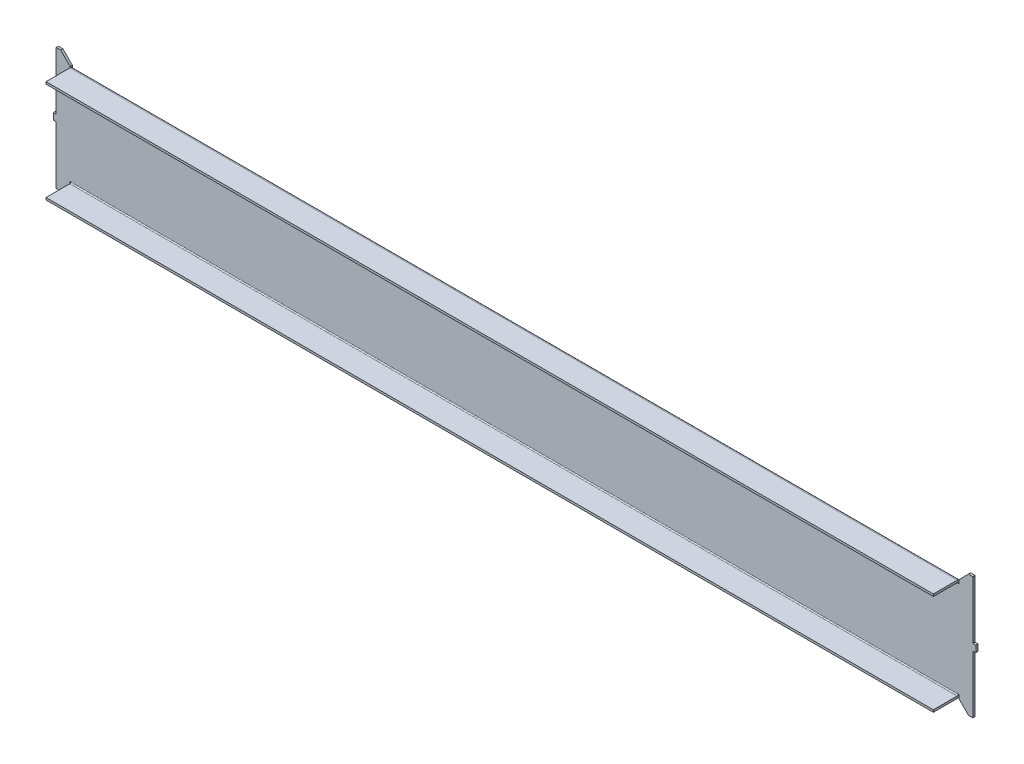
SolidWorks part; units mm, degrees
note: The reader was unsure of these and kept them because the rebuilt part matched: flange length of "Ребро-кромка1".
ref_plane "Спереди" through (0, 0, 0) normal (0, 0, 1) x (1, 0, 0)
ref_plane "Сверху" through (0, 0, 0) normal (0, 1, 0) x (1, 0, 0)
ref_plane "Справа" through (0, 0, 0) normal (1, 0, 0) x (0, 0, -1)
sketch "Эскиз1" plane through (0, 0, 0) normal (0, 0, 1) x (1, 0, 0)
  line L1 (-313, -35) -> (313, -35)
  line L2 (-313, -35) -> (-313, 35)
  line L3 (-313, 35) -> (313, 35)
  line L4 (313, -35) -> (313, 35)
  line L5 (-313, -35) -> (313, 35) construction
  line L6 (-313, 35) -> (313, -35) construction
  point P0 (0, 0)
  dimension "D1" = 70
  dimension "D2" = 626
base flange "Базовая кромка1" sketch "Эскиз1" thickness 1.5 reverse thickness direction no parameters "D1"=0.7366
edge flange "Ребро-кромка1" sketch "Эскиз5" flange profiles "Эскиз5", "Эскиз7" flange angle 90 flange length 18.5 flange position material inside bend radius 0.7366 thickness 1.5 relief rectangular parameters "D6"=10, "D8"=1
sketch "Эскиз5" plane through (0, 35, 0) normal (0, 1, 0) x (-1, 0, 0)
  line L0 (-313, 0) -> (313, 0) construction
  line L1 (-313, 0) -> (313, 0)
  line L2 (-313, 0) -> (-313, 17)
  line L3 (-313, 17) -> (313, 17)
  line L4 (313, 17) -> (313, 0)
sketch "Эскиз7" plane through (0, -35, 0) normal (0, -1, 0) x (1, 0, 0)
  line L0 (-313, 0) -> (313, 0) construction
  line L1 (-313, 0) -> (313, 0)
  line L2 (-313, 0) -> (-313, 17)
  line L3 (-313, 17) -> (313, 17)
  line L4 (313, 17) -> (313, 0)
bend "EdgeBend1" bend radius 0.7366 bend angle 90 parameters "D5"=1
bend "EdgeBend2" bend radius 0.7366 bend angle 90 parameters "D5"=3
sketch "Эскиз8" plane through (0, 0, 0) normal (0, 0, 1) x (1, 0, 0)
  line L0 (-313, 32.7634) -> (-313, -32.7634) construction
  line L1 (-315, 2.25) -> (-313, 2.25)
  line L2 (-315, 2.25) -> (-315, -2.25)
  line L3 (-315, -2.25) -> (-313, -2.25)
  line L4 (-313, 2.25) -> (-313, -2.25)
  line L5 (-315, 2.25) -> (-313, -2.25) construction
  line L6 (-315, -2.25) -> (-313, 2.25) construction
  line L7 (0, 0) -> (0, 80.527) construction
  line L8 (315, -2.25) -> (313, 2.25) construction
  line L9 (315, 2.25) -> (313, -2.25) construction
  line L10 (313, 2.25) -> (313, -2.25)
  line L11 (315, -2.25) -> (313, -2.25)
  line L12 (315, 2.25) -> (315, -2.25)
  line L13 (315, 2.25) -> (313, 2.25)
  point P0 (-314, 0)
  point P14 (314, 0)
  dimension "D1" = 2
  dimension "D2" = 4.5
base flange "Выступ1" sketch "Эскиз8" thickness 1.5 reverse thickness direction no parameters "D1"=0.7366
sketch "Эскиз11" plane through (0, 0, 17) normal (0, 0, 1) x (1, 0, 0)
  line L0 (-313, 32.7634) -> (313, 32.7634) construction
  line L1 (-313, 35) -> (-303, 35)
  line L2 (-313, 35) -> (-313, 32.7634)
  line L3 (-313, 32.7634) -> (-303, 32.7634)
  line L4 (-303, 35) -> (-303, 32.7634)
  line L5 (0, 0) -> (0, 79.6562) construction
  line L6 (0, 0) -> (58.6541, 0) construction
  line L7 (-303, -35) -> (-303, -32.7634)
  line L8 (-313, -32.7634) -> (-303, -32.7634)
  line L9 (-313, -35) -> (-313, -32.7634)
  line L10 (-313, -35) -> (-303, -35)
  line L11 (313, -35) -> (303, -35)
  line L12 (313, -35) -> (313, -32.7634)
  line L13 (313, -32.7634) -> (303, -32.7634)
  line L14 (303, -35) -> (303, -32.7634)
  line L15 (303, 35) -> (303, 32.7634)
  line L16 (313, 32.7634) -> (303, 32.7634)
  line L17 (313, 35) -> (313, 32.7634)
  line L18 (313, 35) -> (303, 35)
  dimension "D1" = 10
extrude "Вырез-Вытянуть1" cut sketch "Эскиз11" against normal up to surface (18.5 mm away) normal cut yes
sketch "Эскиз12" plane through (0, 0, 0) normal (0, 0, 1) x (1, 0, 0)
  line L0 (-313, 32.7634) -> (-313, 41.7634)
  line L1 (-313, 41.7634) -> (-310, 41.7634)
  line L2 (-310, 41.7634) -> (-303.5, 35.2634)
  line L3 (-303.5, 35.2634) -> (-303.5, 32.7634)
  line L4 (-313, 32.7634) -> (-303, 32.7634) construction
  line L5 (-303.5, 32.7634) -> (-313, 32.7634)
  line L6 (-303, 35) -> (-303, 33.5) construction
  line L7 (0, 0) -> (0, 105.8944) construction
  line L8 (0, 0) -> (116.0078, 0) construction
  line L9 (-303.5, -32.7634) -> (-313, -32.7634)
  line L10 (-303.5, -35.2634) -> (-303.5, -32.7634)
  line L11 (-310, -41.7634) -> (-303.5, -35.2634)
  line L12 (-313, -41.7634) -> (-310, -41.7634)
  line L13 (-313, -32.7634) -> (-313, -41.7634)
  line L14 (313, -32.7634) -> (313, -41.7634)
  line L15 (313, -41.7634) -> (310, -41.7634)
  line L16 (310, -41.7634) -> (303.5, -35.2634)
  line L17 (303.5, -35.2634) -> (303.5, -32.7634)
  line L18 (303.5, -32.7634) -> (313, -32.7634)
  line L19 (303.5, 32.7634) -> (313, 32.7634)
  line L20 (303.5, 35.2634) -> (303.5, 32.7634)
  line L21 (310, 41.7634) -> (303.5, 35.2634)
  line L22 (313, 41.7634) -> (310, 41.7634)
  line L23 (313, 32.7634) -> (313, 41.7634)
  dimension "D1" = 0.5
  dimension "D2" = 45
  dimension "D3" = 9
  dimension "D4" = 2.5
base flange "Выступ2" sketch "Эскиз12" thickness 1.5 reverse thickness direction no parameters "D1"=0.7366
sketch "Эскиз13" plane through (0, 0, 0) normal (0, 0, 1) x (1, 0, 0)
  line L0 (-270, 22) -> (-222, 22) construction
  line L1 (-303, 35) -> (-303, 33.5) construction
  line L2 (-303, 33.5) -> (303, 33.5) construction
  line L3 (0, 0) -> (0, 82.9755) construction
  line L4 (270, 22) -> (222, 22) construction
  circle A0 centre (-270, 22) radius 3.25
  circle A1 centre (-222, 22) radius 3.25
  circle A2 centre (222, 22) radius 3.25
  circle A3 centre (270, 22) radius 3.25
  dimension "D1" = 6.5
  dimension "D2" = 48
  dimension "D3" = 33
  dimension "D4" = 11.5
extrude "Вырез-Вытянуть2" cut sketch "Эскиз13" against normal blind 1.5 normal cut yes
sketch "Сгиб-Линии1" [suppressed] plane through (0, 0, 0) normal (0, 1, 0) x (1, 0, 0)
sketch "Граничная рамка1" [suppressed] plane through (0, 0, 0) normal (0, 1, 0) x (1, 0, 0)
sheet metal parameters "Листовой металл3" thickness 1.5 parameters "D1"=0.7366
flat pattern "Развертка3" [suppressed]
sketch "Сгиб-Линии2" plane through (0, 0, 0) normal (0, 1, 0) x (1, 0, 0)
sketch "Граничная рамка2" [suppressed] plane through (0, 0, 0) normal (0, 1, 0) x (1, 0, 0)
sheet metal parameters "Листовой металл7" thickness 1.5 parameters "D1"=0.7366
flat pattern "Развертка3" [suppressed]
sketch "Сгиб-Линии2" plane through (0, 0, 0) normal (0, 1, 0) x (1, 0, 0)
sketch "Граничная рамка2" [suppressed] plane through (0, 0, 0) normal (0, 1, 0) x (1, 0, 0)
bend of the flat pattern "Плоское состояние-<EdgeBend1>1"
bend of the flat pattern "Плоское состояние-<EdgeBend2>1"
sheet metal parameters "Листовой металл8" thickness 1.5 parameters "D1"=0.7366
flat pattern "Развертка8" [suppressed]
sketch "Сгиб-Линии3" plane through (0, 0, 0) normal (0, 1, 0) x (1, 0, 0)
sketch "Граничная рамка3" [suppressed] plane through (0, 0, 0) normal (0, 1, 0) x (1, 0, 0)
bend of the flat pattern "Плоское состояние-<EdgeBend1>2"
bend of the flat pattern "Плоское состояние-<EdgeBend2>2"
sheet metal parameters "Листовой металл9" thickness 1.5 parameters "D1"=0.7366
flat pattern "Развертка8" [suppressed]
sketch "Сгиб-Линии3" plane through (0, 0, 0) normal (0, 1, 0) x (1, 0, 0)
sketch "Граничная рамка3" [suppressed] plane through (0, 0, 0) normal (0, 1, 0) x (1, 0, 0)
bend of the flat pattern "Плоское состояние-<EdgeBend1>2"
bend of the flat pattern "Плоское состояние-<EdgeBend2>2"
sheet metal parameters "Листовой металл10" thickness 1.5 parameters "D1"=0.7366
flat pattern "Развертка10"
sketch "Сгиб-Линии4" plane through (0, 0, 0) normal (0, 0, 1) x (1, 0, 0)
  line L0 (-278, -38.8132) -> (278, -38.8132) construction
  line L1 (278, 38.8132) -> (-278, 38.8132) construction
  line L2 (-278, -38.8132) -> (278, -38.8132) construction
  line L3 (278, 38.8132) -> (-278, 38.8132) construction
sketch3d "Граничная рамка4" [suppressed]
  line L0 (-290, -52.6263, 0) -> (290, -52.6263, 0) construction
  line L1 (-290, 52.6263, 0) -> (290, 52.6263, 0) construction
  line L2 (-290, -52.6263, 0) -> (-290, 52.6263, 0) construction
  line L3 (290, -52.6263, 0) -> (290, 52.6263, 0) construction
bend of the flat pattern "Плоское состояние-<EdgeBend1>3"
bend of the flat pattern "Плоское состояние-<EdgeBend2>3"
sheet metal parameters "Листовой металл11" thickness 1.5 parameters "D1"=0.7366
flat pattern "Развертка10"
sketch "Сгиб-Линии4" plane through (0, 0, 0) normal (0, 0, 1) x (1, 0, 0)
  line L0 (-278, -33.8132) -> (278, -33.8132) construction
  line L1 (278, 33.8132) -> (-278, 33.8132) construction
  line L2 (-278, -33.8132) -> (278, -33.8132) construction
  line L3 (278, 33.8132) -> (-278, 33.8132) construction
sketch3d "Граничная рамка4" [suppressed]
  line L0 (-290, -51.1263, 0) -> (290, -51.1263, 0) construction
  line L1 (-290, 51.1263, 0) -> (290, 51.1263, 0) construction
  line L2 (-290, -51.1263, 0) -> (-290, 51.1263, 0) construction
  line L3 (290, -51.1263, 0) -> (290, 51.1263, 0) construction
bend of the flat pattern "Плоское состояние-<EdgeBend1>3"
bend of the flat pattern "Плоское состояние-<EdgeBend2>3"
